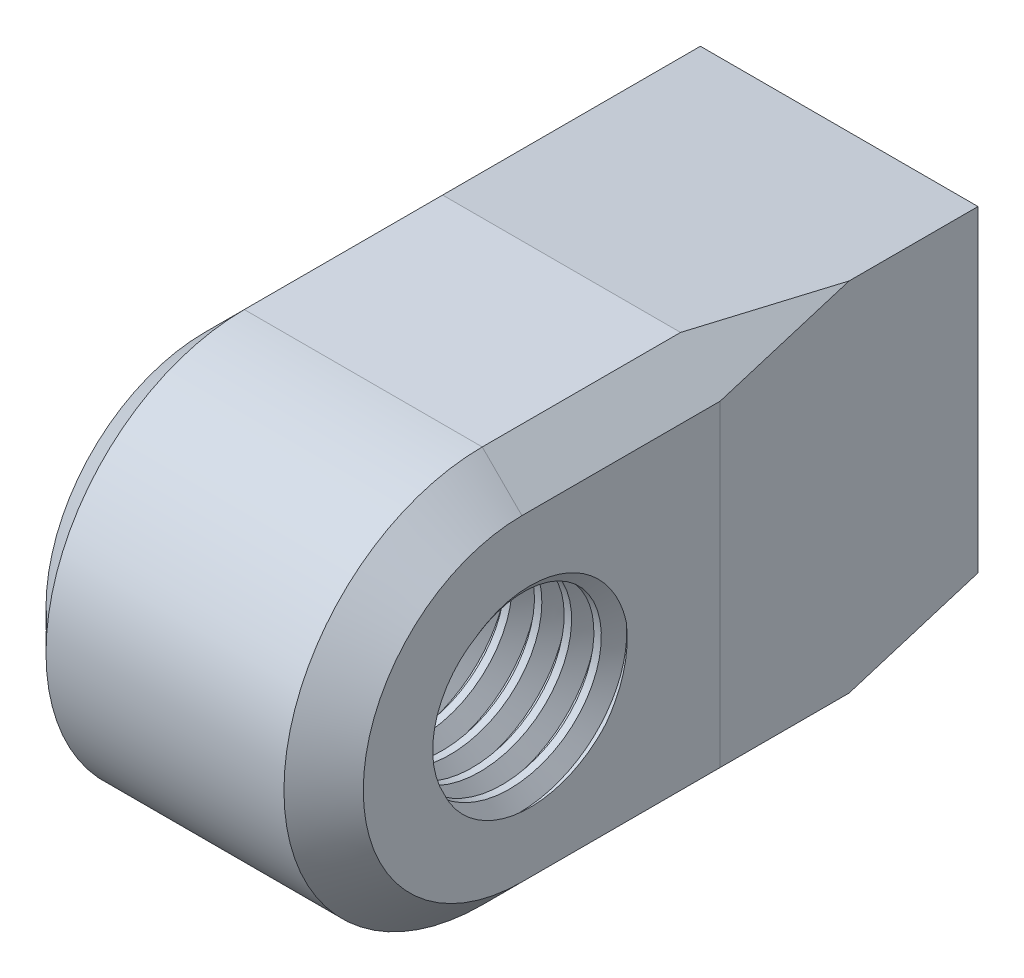
SolidWorks part; units mm, degrees
ref_plane "Front Plane" through (0, 0, 0) normal (0, 0, 1) x (1, 0, 0)
ref_plane "Top Plane" through (0, 0, 0) normal (0, 1, 0) x (1, 0, 0)
ref_plane "Right Plane" through (0, 0, 0) normal (1, 0, 0) x (0, 0, -1)
sketch "Sketch1" plane through (0, 0, 0) normal (1, 0, 0) x (0, -1, 0)
  line L1 (-10, 0) -> (10, 0)
  line L2 (-10, 0) -> (-10, 25)
  line L3 (-10, 25) -> (10, 25)
  line L4 (10, 0) -> (10, 25)
  circle A0 centre (0, 0) radius 4.5
  circle A1 centre (0, 0) radius 10
  dimension "D1" = 9
  dimension "D2" = 20
  dimension "D3" = 25
extrude "Boss-Extrude1" add sketch "Sketch1" along normal blind 16 contours A1 L4 L3 L2 | L1 A1 A0 | L1 A1 A0 region at (0, 0, -4.8368) region at (0, 0, 4.8368) region at (0, 0, -16.2817)
chamfer "Chamfer1" distance 15 distance2 2 3 edges at (8, -10, -25) (8, 10, -25) (16, 0, -25) first distance on face at (8, -10, -12.5) first distance on face at (8, 10, -12.5) first distance on face at (16, 0, -10)
sketch "Sketch2" plane through (0, 0, -25) normal (0, 0, -1) x (-1, 0, 0)
  line L0 (0, 8) -> (0, -8) construction
  line L1 (-16, 10) -> (0, 10) construction
  circle A0 centre (-8, 0) radius 3
  dimension "D1" = 6
  dimension "D2" = 8
  dimension "D3" = 10
extrude "Cut-Extrude1" cut sketch "Sketch2" against normal blind 15
chamfer "Chamfer2" distance 2 angle 45 6 edges at (0, 0, 10) (16, 10, -5) (0, 10, -5) (0, -10, -5) (16, -10, -5) (16, 0, 10)
thread "Thread1" pitch 1.5 method cut profile "Thread Profile1" start angle 0, offset 1, length 0, pitch 1.5, diameter 9
ref_plane "Plane1" through (-1, 0, -4.5) normal (0, -1, 0) x (0, 0, -1)
sketch "Thread Profile1" plane through (-1, 0, -4.5) normal (0, -1, 0) x (0, 0, -1)
  line L0 (0, 0) -> (0, 1.5) construction
  line L1 (0, 0) -> (0.8119, 0.4687)
  line L2 (0.8119, 0.4687) -> (0.8119, 0.6562)
  line L3 (0.8119, 0.6562) -> (0, 1.125)
  line L4 (0.8119, 0.5625) -> (0, 0.5625) construction
  line L11 (0, 0) -> (0, 1.125)
  point P2 (0, 0)
  dimension "Pitch" = 1.5
  dimension "Profile_Angle" = 60
  dimension "Profile_Land" = 0.1875
  dimension "Profile_Height" = 0.8119
sketch "Sketch3" plane through (0, 0, 0) normal (-1, 0, 0) x (0, -1, 0)
  line L0 (-8, -25) -> (8, -25) construction
  circle A0 centre (0.4266, -18) radius 2.25
  dimension "D2" = 4.5
  dimension "D1" = 7
extrude "Cut-Extrude2" cut sketch "Sketch3" against normal up to surface (6.6452 mm away) up to face at (5, 0, -10)
